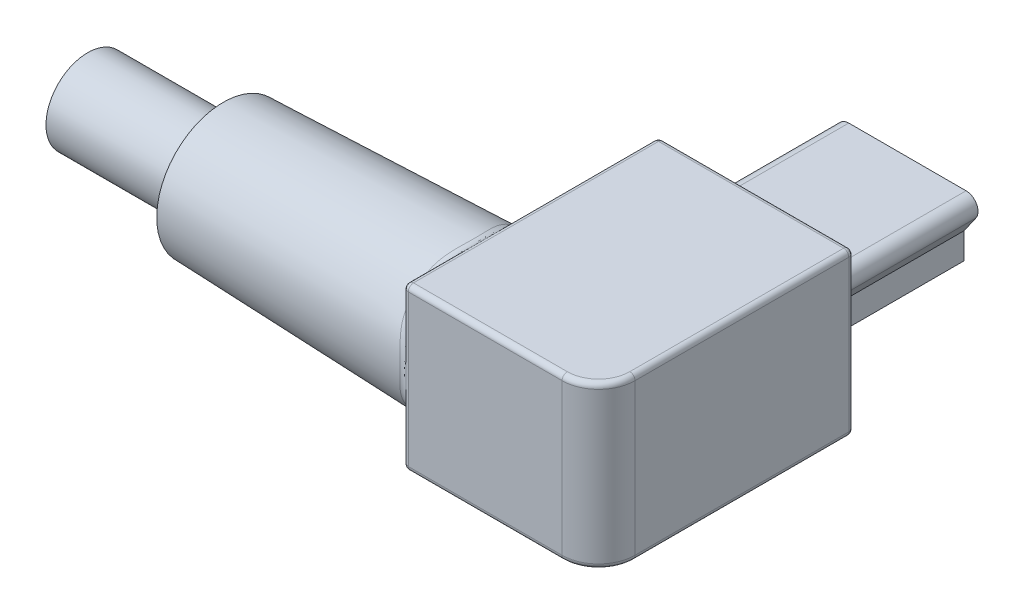
SolidWorks part; units mm, degrees
ref_plane "Front Plane" through (0, 0, 0) normal (0, 0, 1) x (1, 0, 0)
ref_plane "Top Plane" through (0, 0, 0) normal (0, 1, 0) x (1, 0, 0)
ref_plane "Right Plane" through (0, 0, 0) normal (1, 0, 0) x (0, 0, -1)
sketch "Sketch1" plane through (0, 0, 0) normal (0, 0, 1) x (1, 0, 0)
  line L0 (2.7686, 0) -> (-2.7686, 0)
  line L1 (-2.7686, 0) -> (-2.7686, 1.27)
  line L2 (-2.7686, 1.27) -> (-3.3349, 2.0824)
  line L3 (2.8575, 2.9972) -> (-2.8575, 2.9972)
  line L4 (3.3349, 2.0824) -> (2.7686, 1.27)
  line L5 (2.7686, 1.27) -> (2.7686, 0)
  arc A0 (-3.3349, 2.0824) -> (-2.8575, 2.9972) centre (-2.8575, 2.4152) cw
  arc A1 (2.8575, 2.9972) -> (3.3349, 2.0824) centre (2.8575, 2.4152) cw
  point P10 (0, 0)
  point P11 (0, 2.9972)
  dimension "D1" = 5.5372
  dimension "D2" = 2.9972
  dimension "D3" = 1.27
  dimension "D4" = 5.715
extrude "Boss-Extrude1" add sketch "Sketch1" along normal blind 7.366
sketch "Sketch2" plane through (0, 0, 7.366) normal (0, 0, 1) x (1, 0, 0)
  line L0 (-2.7686, 0) -> (2.7686, 0) construction
  line L1 (-4.7625, 5.207) -> (4.7625, 5.207)
  line L2 (-4.7625, 5.207) -> (-4.7625, -2.667)
  line L3 (-4.7625, -2.667) -> (4.7625, -2.667)
  line L4 (4.7625, 5.207) -> (4.7625, -2.667)
  line L5 (-4.7625, 5.207) -> (4.7625, -2.667) construction
  line L6 (-4.7625, -2.667) -> (4.7625, 5.207) construction
  point P0 (0, 1.27)
  dimension "D1" = 9.525
  dimension "D2" = 7.874
  dimension "D3" = 2.667
extrude "Boss-Extrude2" add sketch "Sketch2" along normal blind 12.446
sketch "Sketch3" plane through (-4.7625, 0, 0) normal (-1, 0, 0) x (0, 0, 1)
  circle A0 centre (15.875, 1.27) radius 3.683
  dimension "D1" = 7.366
extrude "Boss-Extrude3" add sketch "Sketch3" along normal blind 12.7 draft 2
fillet "Fillet1" radius 1.778 1 edges at (4.7625, 1.27, 19.812)
fillet "Fillet2" radius 0.254 21 edges at (-4.7625, 1.27, 19.812) (-4.7625, -2.667, 13.589) (-0.889, -2.667, 19.812) (4.2417, -2.667, 19.2912) (-4.7625, 5.207, 13.589) (4.2417, 5.207, 19.2912) (-0.889, 5.207, 19.812) (4.7625, -2.667, 12.7) (4.7625, 5.207, 12.7) (-2.7686, 0.635, 7.366) (-3.0518, 1.6762, 7.366) (-3.3734, 2.6845, 7.366) (0, 2.9972, 7.366) (3.3734, 2.6845, 7.366) (3.0518, 1.6762, 7.366) (2.7686, 0.635, 7.366) (0, 0, 7.366) (0, 5.207, 7.366) (-4.7625, 1.27, 7.366) (0, -2.667, 7.366) (4.7625, 1.27, 7.366)
fillet "Fillet3" radius 0.762 3 edges at (-4.7625, 1.27, 12.192) (-4.7625, -1.3343, 18.4793) (-4.7625, 3.8743, 18.4793)
sketch "Sketch4" plane through (-17.4625, 0, 0) normal (-1, 0, 0) x (0, 0, 1)
  circle A0 centre (15.875, 1.27) radius 2.032
  dimension "D1" = 4.064
extrude "Boss-Extrude4" add sketch "Sketch4" along normal blind 6.604
